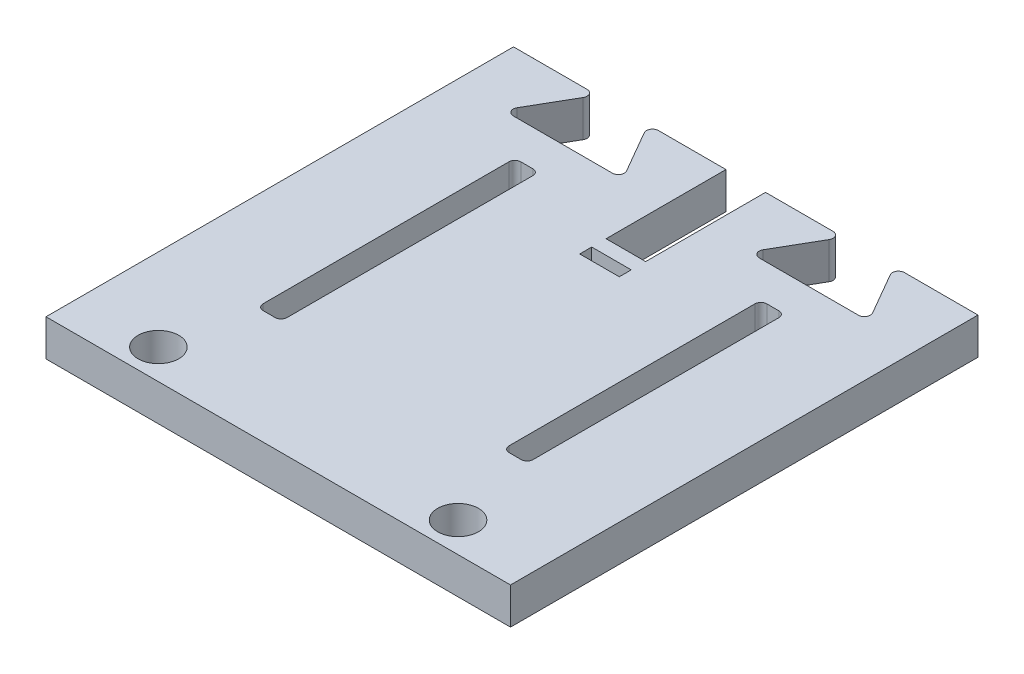
SolidWorks part; units mm, degrees
ref_plane "Front Plane" through (0, 0, 0) normal (0, 0, 1) x (1, 0, 0)
ref_plane "Top Plane" through (0, 0, 0) normal (0, 1, 0) x (1, 0, 0)
ref_plane "Right Plane" through (0, 0, 0) normal (1, 0, 0) x (0, 0, -1)
sketch "Sketch1" plane through (0, 0, 0) normal (0, 1, 0) x (1, 0, 0)
  line L0 (-19.375, 0) -> (-19.375, 39)
  line L1 (-19.375, 39) -> (-12.375, 39)
  line L2 (-12.375, 39) -> (-15.2618, 34)
  line L3 (-15.2618, 34) -> (-5.2618, 34)
  line L4 (-5.2618, 34) -> (-8.1485, 39)
  line L5 (-8.1485, 39) -> (8.1485, 39)
  line L6 (8.1485, 39) -> (5.2618, 34)
  line L7 (5.2618, 34) -> (15.2618, 34)
  line L8 (15.2618, 34) -> (12.375, 39)
  line L9 (12.375, 39) -> (19.375, 39)
  line L10 (19.375, 39) -> (19.375, 0)
  line L11 (19.375, 0) -> (-19.375, 0)
  point P3 (0, 0)
  dimension "D1" = 39
  dimension "D2" = 38.75
  dimension "D3" = 7
  dimension "D4" = 10
  dimension "D5" = 10
  dimension "D6" = 7
  dimension "D7" = 5
  dimension "D11" = 60
  dimension "D12" = 60
  dimension "D13" = 60
extrude "Boss-Extrude1" add sketch "Sketch1" along normal blind 3.05
fillet "Fillet3" radius 0.5 8 edges at (15.2618, 1.525, -34) (12.375, 1.525, -39) (5.2618, 1.525, -34) (8.1485, 1.525, -39) (-8.1485, 1.525, -39) (-5.2618, 1.525, -34) (-15.2618, 1.525, -34) (-12.375, 1.525, -39)
sketch "Sketch2" plane through (0, 3.05, 0) normal (0, 1, 0) x (1, 0, 0)
  line L0 (0, 0) -> (0, 32.5) construction
  line L3 (1.65, 29) -> (-1.65, 29)
  line L4 (1.65, 29) -> (1.65, 76)
  line L5 (1.65, 76) -> (-1.65, 76)
  line L6 (-1.65, 29) -> (-1.65, 76)
  line L7 (-1.65, 27.8) -> (1.65, 27.8)
  line L8 (-1.65, 27.8) -> (-1.65, 26.8)
  line L9 (-1.65, 26.8) -> (1.65, 26.8)
  line L10 (1.65, 27.8) -> (1.65, 26.8)
  line L11 (-19.375, 0) -> (19.375, 0) construction
  line L12 (-19.375, 0) -> (-19.375, 82.5) construction
  line L13 (-19.375, 82.5) -> (19.375, 82.5) construction
  line L14 (19.375, 0) -> (19.375, 82.5) construction
  point P8 (0, 29)
  point P13 (0, 27.8)
  dimension "D1" = 3.3
  dimension "D2" = 47
  dimension "D3" = 1
  dimension "D4" = 1.2
  dimension "D5" = 82.5
  dimension "D6" = 6.5
extrude "Cut-Extrude1" cut sketch "Sketch2" against normal through all
sketch "Sketch6" plane through (0, 3.05, 0) normal (0, 1, 0) x (1, 0, 0)
  line L0 (0, 0) -> (0, 18.0616) construction
  line L1 (-6.1278, 34) -> (-14.3957, 34) construction
  line L2 (-11.2618, 31) -> (-9.2618, 31)
  line L3 (-11.2618, 31) -> (-11.2618, 9.5)
  line L4 (-11.2618, 9.5) -> (-9.2618, 9.5)
  line L5 (-9.2618, 31) -> (-9.2618, 9.5)
  line L7 (11.2618, 9.5) -> (9.2618, 9.5)
  line L8 (9.2618, 31) -> (9.2618, 9.5)
  line L9 (11.2618, 31) -> (9.2618, 31)
  line L10 (11.2618, 31) -> (11.2618, 9.5)
  line L11 (-19.375, 0) -> (19.375, 0) construction
  point P9 (-10.2618, 34)
  point P10 (-10.2618, 31)
  dimension "D1" = 2
  dimension "D2" = 3
  dimension "D3" = 9.5
extrude "Cut-Extrude2" cut sketch "Sketch6" against normal through all
fillet "Fillet4" radius 0.5 8 edges at (9.2618, 1.525, -9.5) (11.2618, 1.525, -9.5) (11.2618, 1.525, -31) (9.2618, 1.525, -31) (-11.2618, 1.525, -9.5) (-9.2618, 1.525, -9.5) (-9.2618, 1.525, -31) (-11.2618, 1.525, -31)
sketch "Head Mounting Hole Locations" plane through (0, 3.05, 0) normal (0, 1, 0) x (1, 0, 0)
  line L0 (0, 0) -> (0, 16.3288) construction
  line L1 (-19.375, 0) -> (19.375, 0) construction
  circle A0 centre (-12.5, 2.5) radius 1.5
  circle A1 centre (12.5, 2.5) radius 1.5
  dimension "D1" = 3
  dimension "D2" = 12.5
  dimension "D3" = 2.5
hole_wizard "M3 Clearance Head Mounting Holes" positions "Sketch4" profile "Sketch5" hole size "M3" standard "ANSI Metric" end condition through all
sketch "Sketch4" plane through (0, 3.05, 0) normal (0, 1, 0) x (1, 0, 0)
  point P0 (-12.5, 2.5)
  point P3 (12.5, 2.5)
sketch "Sketch5" plane through (-12.5, 3.05, -2.5) normal (1, 0, 0) x (0, 0, 1)
  line L0 (0, 0) -> (0, 3.05)
  line L1 (0, 3.05) -> (1.7, 3.05)
  line L2 (1.7, 3.05) -> (1.7, 0)
  line L5 (1.7, 0) -> (0, 0)
  line L11 (0, -6.35) -> (0, 107.95) construction
  dimension "Thru Hole Dia." = 3.4
  dimension "Thru Hole Depth" = 3.05
sketch "Sketch7" plane through (0, 3.05, 0) normal (0, 1, 0) x (1, 0, 0)
  line L0 (-19.375, 39) -> (-18.875, 39)
  line L1 (-13.241, 39) -> (-19.375, 39) construction
  line L2 (-18.875, 39) -> (-18.875, 0)
  line L3 (-19.375, 0) -> (19.375, 0) construction
  line L4 (-18.875, 0) -> (-19.375, 0)
  line L5 (-19.375, 0) -> (-19.375, 39)
  line L6 (19.375, 39) -> (18.875, 39)
  line L7 (19.375, 39) -> (13.241, 39) construction
  line L8 (18.875, 39) -> (18.875, 0)
  line L9 (18.875, 0) -> (19.375, 0)
  line L10 (19.375, 0) -> (19.375, 39)
  dimension "D1" = 0.5
  dimension "D2" = 0.5
extrude "Cut-Extrude3" [suppressed] cut sketch "Sketch7" against normal through all
